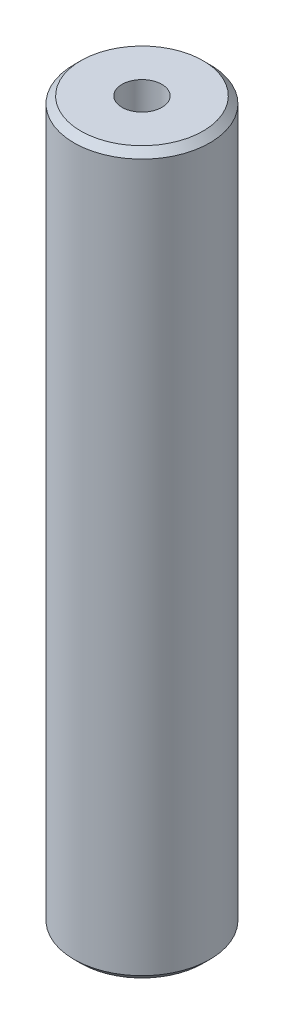
SolidWorks part; units mm, degrees
ref_plane "Front Plane" through (0, 0, 0) normal (0, 0, 1) x (1, 0, 0)
ref_plane "Top Plane" through (0, 0, 0) normal (0, 1, 0) x (1, 0, 0)
ref_plane "Right Plane" through (0, 0, 0) normal (1, 0, 0) x (0, 0, -1)
sketch "Sketch1" plane through (0, 0, 0) normal (0, 1, 0) x (1, 0, 0)
  circle A0 centre (0, 0) radius 10
  dimension "SHAFT_OD" = 20
extrude "Boss-Extrude1" add sketch "Sketch1" along normal blind 106.1731
sketch "Sketch2" plane through (0, 0, 0) normal (0, 1, 0) x (1, 0, 0)
  circle A0 centre (0, 0) radius 2.9401
  dimension "BORE_D" = 5.8803
extrude "Cut-Extrude1" cut sketch "Sketch2" along normal through all
chamfer "Chamfer1" distance 1.0036 angle 45 2 edges at (0, 106.1731, 10) (0, 0, 10)
